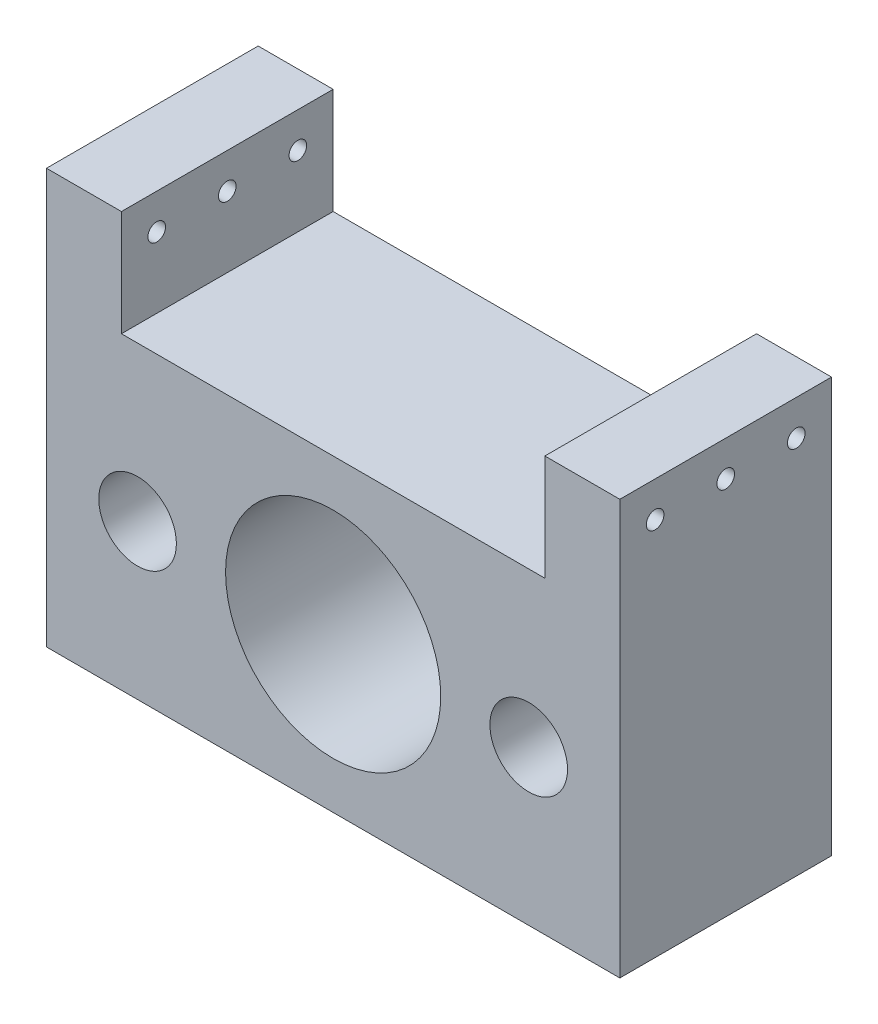
SolidWorks part; units mm, degrees
ref_plane "Front Plane" through (0, 0, 0) normal (0, 0, 1) x (1, 0, 0)
ref_plane "Top Plane" through (0, 0, 0) normal (0, 1, 0) x (1, 0, 0)
ref_plane "Right Plane" through (0, 0, 0) normal (1, 0, 0) x (0, 0, -1)
sketch "Sketch1" plane through (0, 0, 0) normal (0, 0, 1) x (1, 0, 0)
  line L0 (0, -55) -> (0, 55) construction
  line L1 (-32.5, 17.5) -> (32.5, 17.5)
  line L2 (-32.5, 17.5) -> (-32.5, -17.5)
  line L3 (-32.5, -17.5) -> (32.5, -17.5)
  line L4 (32.5, 17.5) -> (32.5, -17.5)
  line L6 (32.5, 29.5) -> (24, 29.5)
  line L7 (-32.5, 17.5) -> (-24, 17.5)
  line L8 (-32.5, 17.5) -> (-32.5, 29.5)
  line L9 (-32.5, 29.5) -> (-24, 29.5)
  line L10 (-24, 17.5) -> (-24, 29.5)
  line L11 (24, 17.5) -> (24, 29.5)
  line L12 (32.5, 17.5) -> (24, 17.5)
  line L13 (32.5, 17.5) -> (32.5, 29.5)
  circle A0 centre (0, 0) radius 5
  circle A1 centre (0, 8) radius 1.5
  circle A2 centre (8, 0) radius 1.5
  circle A3 centre (0, -8) radius 1.5
  circle A4 centre (-8, 0) radius 1.5
  circle A5 centre (-22.1713, 0) radius 4.4
  circle A6 centre (22.1713, 0) radius 4.4
  circle A11 centre (0, 0) radius 12.1964
  point P15 (0, 17.5)
  point P18 (-32.5, 0)
  point P33 (0, 0)
  dimension "D3" = 10
  dimension "D4" = 8.8
  dimension "D5" = 12
  dimension "D6" = 24
  dimension "D1" = 65
  dimension "D2" = 35
extrude "Boss-Extrude1" add sketch "Sketch1" along normal blind 24 contours L4 L1 L2 L3 A0 A5 A6 | L8 L7 L10 L9 | L13 L6 L11 L12 region at (-28.25, 16.7618, 0)
extrude "Boss-Extrude2" add sketch "Sketch1<3>" along normal blind 5 contours A11 A4 A3 A2 A1 A0 region at (-11.8515, 0, 0)
sketch "Sketch1<3>" plane through (0, 0, 0) normal (0, 0, 1) x (1, 0, 0) same geometry as "Sketch1"
sketch "Sketch2" plane through (0, 0, 0) normal (1, 0, 0) x (0, 0, -1)
  line L0 (-24, 29.5) -> (0, 29.5) construction
  circle A0 centre (-20, 25.5) radius 1
  circle A1 centre (-12, 25.5) radius 1
  circle A2 centre (-4, 25.5) radius 1
  point P3 (-10.2847, 22.8781)
  point P9 (-12, 29.5)
  dimension "D1" = 2
  dimension "D3" = 4
  dimension "D2" = 3
extrude "Cut-Extrude1" cut sketch "Sketch2" against normal through all both and the other way through all
